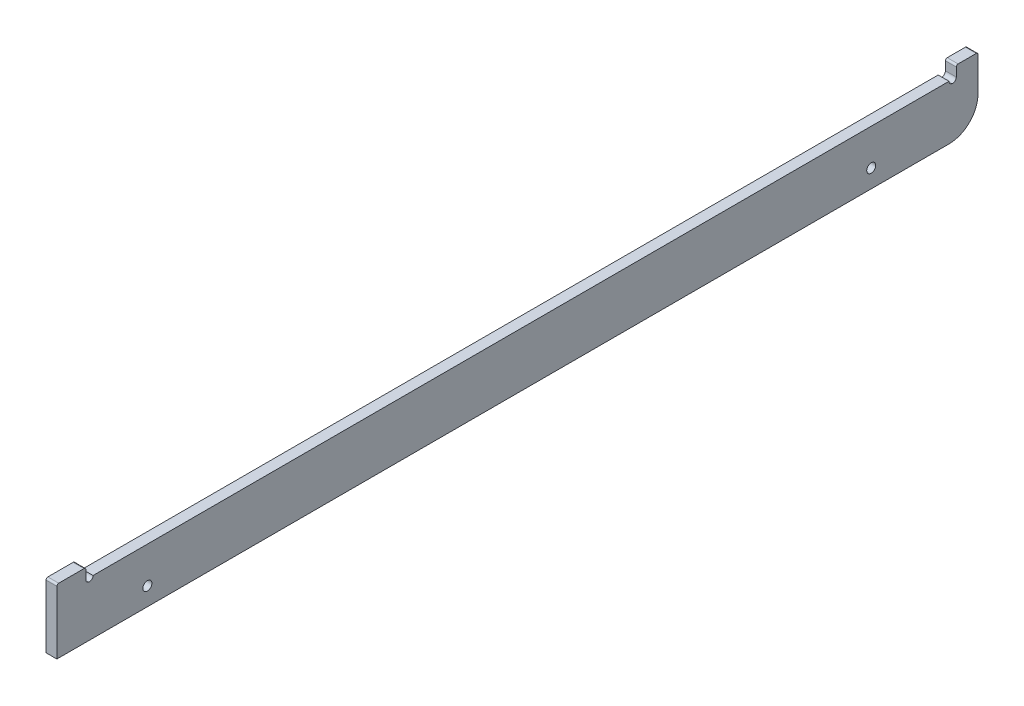
SolidWorks part; units mm, degrees
ref_plane "정면" through (0, 0, 0) normal (0, 0, 1) x (1, 0, 0)
ref_plane "윗면" through (0, 0, 0) normal (0, 1, 0) x (1, 0, 0)
ref_plane "우측면" through (0, 0, 0) normal (1, 0, 0) x (0, 0, -1)
sketch "스케치1" plane through (0, 0, 0) normal (1, 0, 0) x (0, 0, -1)
  line L1 (0, 0) -> (254.5, 0)
  line L2 (0, 0) -> (0, 15)
  line L3 (0, 15) -> (254.5, 15)
  line L4 (254.5, 0) -> (254.5, 15)
  dimension "D1" = 254.5
  dimension "D2" = 15
extrude "보스-돌출1" add sketch "스케치1" along normal blind 3
sketch "스케치2" plane through (3, 0, 0) normal (1, 0, 0) x (0, 0, -1)
  line L0 (-2.5, 18) -> (292.5, 18) construction
  line L1 (0, 15) -> (8, 15)
  line L2 (0, 15) -> (0, 18)
  line L3 (0, 18) -> (8, 18)
  line L4 (8, 15) -> (8, 18)
  line L6 (254.5, 15) -> (248.5, 15)
  line L7 (254.5, 15) -> (254.5, 18)
  line L8 (254.5, 18) -> (248.5, 18)
  line L9 (248.5, 15) -> (248.5, 18)
  dimension "D1" = 6
  dimension "D2" = 8
extrude "보스-돌출2" add sketch "스케치2" against normal blind 3
sketch "스케치3" plane through (3, 0, 0) normal (1, 0, 0) x (0, 0, -1)
  line L4 (248.5, 15) -> (8, 15) construction
  line L5 (8, 15) -> (8, 18) construction
  line L6 (248.5, 18) -> (248.5, 15) construction
  circle A0 centre (9, 15) radius 1
  circle A1 centre (247.5, 15) radius 1
  dimension "D1" = 2
extrude "컷-돌출1" cut sketch "스케치3" against normal blind 3
sketch "스케치4" plane through (3, 0, 0) normal (1, 0, 0) x (0, 0, -1)
  line L0 (28.05, 5) -> (25, 5) construction
  line L1 (25, 5) -> (21.95, 5) construction
  line L2 (228.05, 5) -> (225, 5) construction
  line L3 (225, 5) -> (221.95, 5) construction
  arc A0 (26.5, 3.45) -> (26.5, 6.55) centre (26.5, 5) ccw construction
  arc A1 (23.5, 6.55) -> (23.5, 3.45) centre (23.5, 5) ccw construction
  arc A2 (226.5, 3.45) -> (226.5, 6.55) centre (226.5, 5) ccw construction
  arc A3 (223.5, 6.55) -> (223.5, 3.45) centre (223.5, 5) ccw construction
  circle A4 centre (225, 5) radius 1.25
  circle A5 centre (25, 5) radius 1.25
  dimension "D1" = 2.5
extrude "컷-돌출2" cut sketch "스케치4" against normal blind 10
fillet "필렛2" radius 8 1 edges at (1.5, 0, -254.5)
fillet "필렛1" [suppressed] radius 0.5
sketch "스케치5" plane through (3, 0, 0) normal (1, 0, 0) x (0, 0, -1)
  line L1 (0, 18) -> (255.7652, 18)
  line L2 (0, 18) -> (0, 17.9)
  line L3 (0, 17.9) -> (255.7652, 17.9)
  line L4 (255.7652, 18) -> (255.7652, 17.9)
  dimension "D1" = 0.1
extrude "컷-돌출3" cut sketch "스케치5" against normal blind 10
fillet "필렛3" radius 0.5 4 edges at (1.5, 17.9, 0) (1.5, 17.9, -8) (1.5, 17.9, -248.5) (1.5, 17.9, -254.5)
